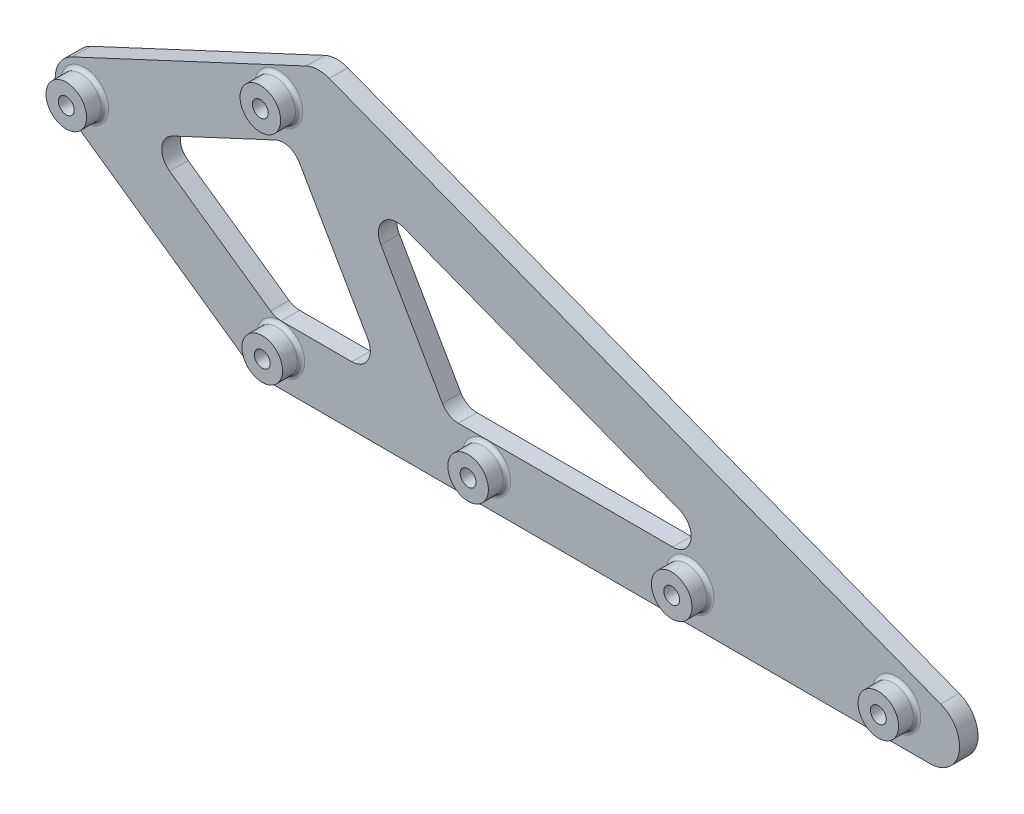
SolidWorks part; units mm, degrees
ref_plane "Front" through (0, 0, 0) normal (0, 0, 1) x (1, 0, 0)
ref_plane "Top" through (0, 0, 0) normal (0, 1, 0) x (1, 0, 0)
ref_plane "Right" through (0, 0, 0) normal (1, 0, 0) x (0, 0, -1)
sketch "Sketch1" plane through (0, 0, 0) normal (0, 0, 1) x (1, 0, 0)
  line L0 (0, 0) -> (180, 0) construction
  line L1 (0, 8) -> (180, 8)
  line L2 (0, -8) -> (180, -8)
  line L3 (0, 0) -> (-49.1491, 34.4146) construction
  line L4 (-4.5886, -6.5532) -> (-53.7377, 27.8614)
  line L5 (4.5886, 6.5532) -> (-44.5605, 40.9678)
  line L6 (-49.1491, 34.4146) -> (14.2924, 63.9979) construction
  line L7 (-52.5301, 41.665) -> (10.9115, 71.2483)
  line L8 (-45.7682, 27.1641) -> (17.6734, 56.7474)
  line L9 (14.2924, 63.9979) -> (180, 0) construction
  line L10 (17.1746, 71.4606) -> (182.8822, 7.4628)
  line L11 (11.4102, 56.5351) -> (177.1178, -7.4628)
  arc A0 (0, 8) -> (0, -8) centre (0, 0) ccw
  arc A1 (180, -8) -> (180, 8) centre (180, 0) ccw
  arc A2 (-4.5886, -6.5532) -> (4.5886, 6.5532) centre (0, 0) ccw
  arc A3 (-44.5605, 40.9678) -> (-53.7377, 27.8614) centre (-49.1491, 34.4146) ccw
  arc A4 (-52.5301, 41.665) -> (-45.7682, 27.1641) centre (-49.1491, 34.4146) ccw
  arc A5 (17.6734, 56.7474) -> (10.9115, 71.2483) centre (14.2924, 63.9979) ccw
  arc A6 (17.1746, 71.4606) -> (11.4102, 56.5351) centre (14.2924, 63.9979) ccw
  arc A7 (177.1178, -7.4628) -> (182.8822, 7.4628) centre (180, 0) ccw
  point P3 (90, 0)
  point P10 (-24.5746, 17.2073)
  point P17 (-17.4284, 49.2062)
  point P24 (97.1462, 31.9989)
  dimension "D2" = 8
  dimension "D1" = 180
  dimension "D3" = 60
  dimension "D4" = 35
  dimension "D5" = 70
  dimension "D6" = 25
extrude "Boss-Extrude1" add sketch "Sketch1" along normal blind 5 contours A6 L7 A3 L5 L8 L11 | A5 L8 L11 L1 A1 L10 | A7 L11 L1 L5 A2 L2 | A4 L4 A0 L1 L5 L8 | L11 A7 A1 L1 | A5 A6 L11 L8 | A3 A4 L8 L5 | A0 A2 L5 L1 region at (-23.7091, 16.2142, 0) region at (0.0076, 0.0241, 0) region at (82.5266, -0.3671, 0) region at (90.3429, 35.0292, 0) region at (169.582, 1.9419, 0) region at (-47.3454, 34.2568, 0) region at (-16.397, 49.9813, 0) region at (14.2944, 63.9381, 0)
sketch "Sketch2" plane through (0, 0, 5) normal (0, 0, 1) x (1, 0, 0)
  line L0 (-33.21, 33.0201) -> (14.587, 55.3082) construction
  line L1 (2.5224, 8) -> (-33.21, 33.0201) construction
  line L2 (2.5224, 8) -> (137.0806, 8) construction
  line L3 (14.587, 55.3082) -> (137.0806, 8) construction
  line L4 (-33.21, 33.0201) -> (14.587, 55.3082)
  line L5 (2.5224, 8) -> (-33.21, 33.0201)
  line L6 (2.5224, 8) -> (137.0806, 8)
  line L7 (14.587, 55.3082) -> (137.0806, 8)
  line L8 (6.7404, 51.6493) -> (31.9413, 8)
  line L9 (24.0609, 51.6493) -> (49.2618, 8)
  line M15 (14.587, 55.3082) -> (137.0806, 8)
  dimension "D1" = 60
  dimension "D2" = 15
extrude "Boss-Extrude2" add sketch "Sketch2" against normal through all contours L9 L4 L8 L6 M15 region at (27.4833, 30.7516, 5)
fillet "Fillet1" radius 5 7 edges at (137.0806, 8, 2.5) (24.0609, 51.6493, 2.5) (49.2618, 8, 2.5) (31.9413, 8, 2.5) (2.5224, 8, 2.5) (-33.21, 33.0201, 2.5) (6.7404, 51.6493, 2.5)
sketch "Sketch3" plane through (0, 0, 5) normal (0, 0, 1) x (1, 0, 0)
  line L0 (-49.1491, 34.4146) -> (3.9817, 1.5) construction
  line L1 (-4.5886, -6.5532) -> (-53.7377, 27.8614) construction
  line L2 (-4.5886, -6.5532) -> (-53.7377, 27.8614)
  line L3 (3.9817, 1.5) -> (59.7817, 1.5) construction
  line L4 (59.7817, 1.5) -> (114.9817, 1.5) construction
  line L5 (0, -8) -> (180, -8) construction
  line L6 (0, -8) -> (180, -8)
  line L7 (114.9817, 1.5) -> (170.9817, 1.5) construction
  line L8 (-49.1491, 34.4146) -> (3.4592, 60) construction
  line L9 (-52.5301, 41.665) -> (10.9115, 71.2483) construction
  line L10 (-52.5301, 41.665) -> (10.9115, 71.2483)
  arc A0 (-52.5301, 41.665) -> (-53.7377, 27.8614) centre (-49.1491, 34.4146) ccw construction
  arc A1 (-52.5301, 41.665) -> (-53.7377, 27.8614) centre (-49.1491, 34.4146) ccw
  circle A2 centre (-49.1491, 34.4146) radius 2.15
  circle A3 centre (-49.1491, 34.4146) radius 5.5
  circle A4 centre (3.9817, 1.5) radius 5.5
  circle A5 centre (3.9817, 1.5) radius 2.15
  circle A6 centre (59.7817, 1.5) radius 2.15
  circle A7 centre (59.7817, 1.5) radius 5.5
  circle A8 centre (114.9817, 1.5) radius 2.15
  circle A9 centre (114.9817, 1.5) radius 5.5
  circle A10 centre (170.9817, 1.5) radius 2.15
  circle A11 centre (170.9817, 1.5) radius 5.5
  circle A12 centre (3.4592, 60) radius 5.5
  circle A13 centre (3.4592, 60) radius 2.15
  dimension "D1" = 11
  dimension "D2" = 4.3
  dimension "D3" = 62.5
  dimension "D4" = 55.8
  dimension "D5" = 111
  dimension "D6" = 167
  dimension "D7" = 58.5
  dimension "D8" = 9.5
  dimension "D9" = 68
extrude "Boss-Extrude3" add sketch "Sketch3" along normal blind 5 contours A3 A2 | A4 | A7 | A9 | A11 | A5 | A6 | A8 | A10 | A12 | A13 region at (-54.4936, 34.4146, 5)
sketch "Sketch4" plane through (0, 0, 5) normal (0, 0, 1) x (1, 0, 0)
  circle A0 centre (-49.1491, 34.4146) radius 2.15 construction
  circle A1 centre (-49.1491, 34.4146) radius 2.15
  circle A2 centre (3.9817, 1.5) radius 2.15 construction
  circle A3 centre (3.9817, 1.5) radius 2.15
  circle A4 centre (59.7817, 1.5) radius 2.15 construction
  circle A5 centre (59.7817, 1.5) radius 2.15
  circle A6 centre (114.9817, 1.5) radius 2.15 construction
  circle A7 centre (114.9817, 1.5) radius 2.15
  circle A8 centre (170.9817, 1.5) radius 2.15 construction
  circle A9 centre (170.9817, 1.5) radius 2.15
  circle A10 centre (3.4592, 60) radius 2.15 construction
  circle A11 centre (3.4592, 60) radius 2.15
extrude "Cut-Extrude1" cut sketch "Sketch4" against normal through all
sketch "Sketch5" plane through (0, 0, 0) normal (0, 0, -1) x (-1, 0, 0)
  circle A0 centre (-114.9817, 1.5) radius 2.15 construction
  circle A1 centre (-59.7817, 1.5) radius 2.15 construction
  circle A2 centre (-3.9817, 1.5) radius 2.15 construction
  circle A3 centre (49.1491, 34.4146) radius 2.15 construction
  circle A4 centre (-3.4592, 60) radius 2.15 construction
  circle A5 centre (-114.9817, 1.5) radius 2.15
  circle A6 centre (-59.7817, 1.5) radius 2.15
  circle A7 centre (-3.9817, 1.5) radius 2.15
  circle A8 centre (49.1491, 34.4146) radius 2.15
  circle A9 centre (-3.4592, 60) radius 2.15
  circle A10 centre (-170.9817, 1.5) radius 2.15 construction
  circle A11 centre (-170.9817, 1.5) radius 2.15
  circle A12 centre (-3.4592, 60) radius 4
  circle A13 centre (49.1491, 34.4146) radius 4
  circle A14 centre (-3.9817, 1.5) radius 4
  circle A15 centre (-59.7817, 1.5) radius 4
  circle A16 centre (-114.9817, 1.5) radius 4
  circle A17 centre (-170.9817, 1.5) radius 4
  dimension "D1" = 8
extrude "Cut-Extrude2" cut sketch "Sketch5" against normal blind 5
fillet "Fillet2" radius 1 6 edges at (176.4817, 1.5, 5) (120.4817, 1.5, 5) (65.2817, 1.5, 5) (9.4817, 1.5, 5) (-43.6491, 34.4146, 5) (8.9592, 60, 5)
